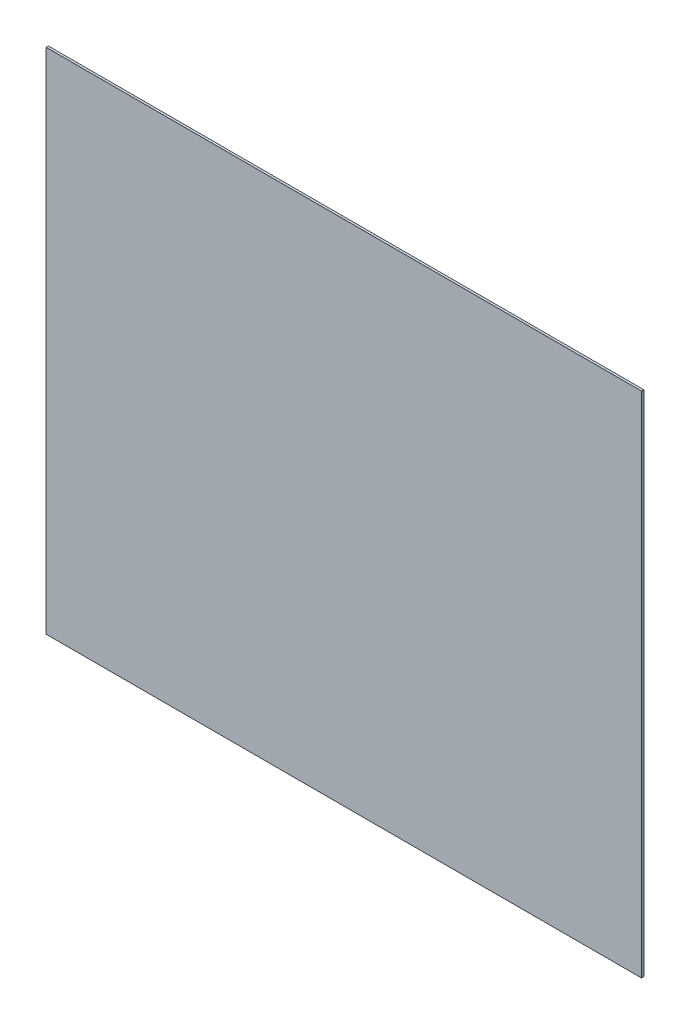
SolidWorks part; units mm, degrees
material "Mahogany"
ref_plane "Front Plane" through (0, 0, 0) normal (0, 0, 1) x (1, 0, 0)
ref_plane "Top Plane" through (0, 0, 0) normal (0, 1, 0) x (1, 0, 0)
ref_plane "Right Plane" through (0, 0, 0) normal (1, 0, 0) x (0, 0, -1)
sketch "Sketch1" plane through (0, 0, 0) normal (0, 0, 1) x (1, 0, 0)
  line L1 (-410, -350) -> (410, -350)
  line L2 (-410, -350) -> (-410, 350)
  line L3 (-410, 350) -> (410, 350)
  line L4 (410, -350) -> (410, 350)
  line L5 (-410, -350) -> (410, 350) construction
  line L6 (-410, 350) -> (410, -350) construction
  point P0 (0, 0)
  dimension "D1" = 820
  dimension "D2" = 700
extrude "Boss-Extrude1" add sketch "Sketch1" along normal blind 3.175
equation "\"W\"= 1700"
equation "\"L\"= 780"
equation "\"H\"= 780"
equation "\"ARM_BOLT_SPACING\"= 166"
equation "\"ARM_TO_WALL\"= 200"
equation "\"D1@Sketch1\"=(\"W\"/2)-30"
equation "\"D2@Sketch1\"=\"H\"-80"
